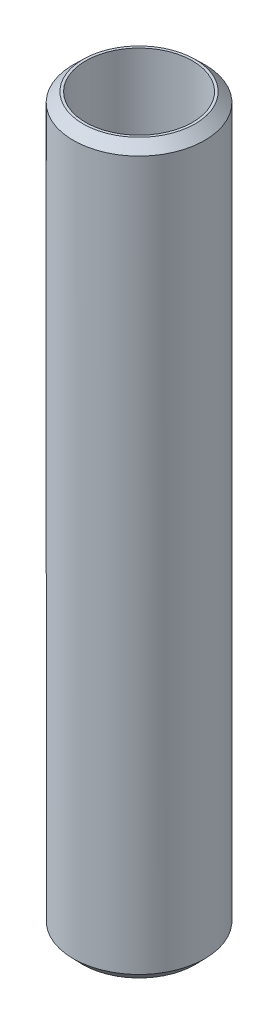
SolidWorks part; units mm, degrees
ref_plane "Front Plane" through (0, 0, 0) normal (0, 0, 1) x (1, 0, 0)
ref_plane "Top Plane" through (0, 0, 0) normal (0, 1, 0) x (1, 0, 0)
ref_plane "Right Plane" through (0, 0, 0) normal (1, 0, 0) x (0, 0, -1)
sketch "Sketch1" plane through (0, 0, 0) normal (0, 1, 0) x (1, 0, 0)
  circle A0 centre (0, 0) radius 32.5
  dimension "SHAFT_OD" = 65
extrude "Boss-Extrude1" add sketch "Sketch1" along normal blind 360.1409
sketch "Sketch2" plane through (0, 0, 0) normal (0, 1, 0) x (1, 0, 0)
  circle A0 centre (0, 0) radius 26.4204
  dimension "BORE_D" = 52.8409
extrude "Cut-Extrude1" cut sketch "Sketch2" along normal through all
chamfer "Chamfer1" distance 4.6669 angle 45.867 2 edges at (0, 360.1409, 32.5) (0, 0, 32.5) first distance on face at (0, 360.1409, 32.5) first distance on face at (0, 0, 26.4204)
